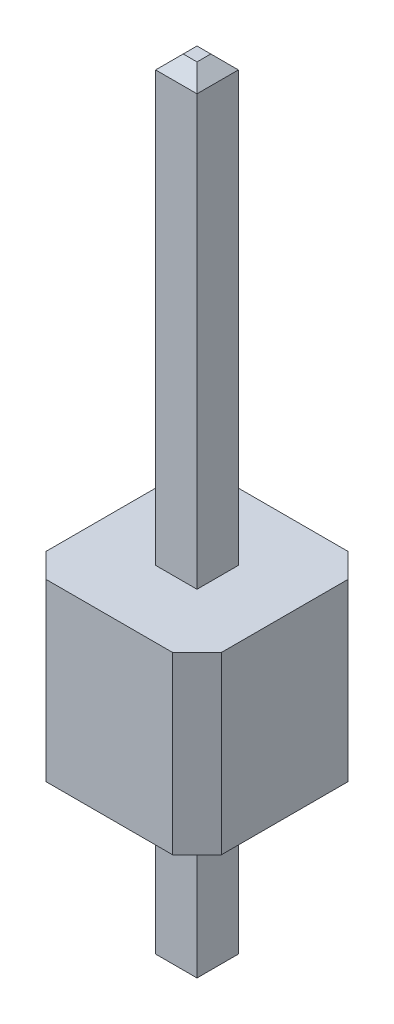
SolidWorks part; units mm, degrees
ref_plane "Alzado" through (0, 0, 0) normal (0, 0, 1) x (1, 0, 0)
ref_plane "Planta" through (0, 0, 0) normal (0, 1, 0) x (1, 0, 0)
ref_plane "Vista lateral" through (0, 0, 0) normal (1, 0, 0) x (0, 0, -1)
sketch "Sketch3" plane through (0, 0, 0) normal (0, 1, 0) x (1, 0, 0)
  line L1 (0.3, -0.3) -> (-0.3, -0.3)
  line L2 (0.3, -0.3) -> (0.3, 0.3)
  line L3 (0.3, 0.3) -> (-0.3, 0.3)
  line L4 (-0.3, -0.3) -> (-0.3, 0.3)
  line L5 (0.3, -0.3) -> (-0.3, 0.3) construction
  line L6 (0.3, 0.3) -> (-0.3, -0.3) construction
  point P0 (0, 0)
  dimension "D1" = 0.6
extrude "Boss-Extrude3" add sketch "Sketch3" along normal blind 11.5
chamfer "Chamfer2" distance 0.2 angle 45 8 edges at (0, 11.5, -0.3) (0.3, 11.5, 0) (0, 11.5, 0.3) (-0.3, 11.5, 0) (0, 0, 0.3) (0.3, 0, 0) (0, 0, -0.3) (-0.3, 0, 0)
ref_plane "Plane2" through (0, 2.54, 0) normal (0, 1, 0) x (1, 0, 0)
sketch "Sketch2" plane through (0, 2.54, 0) normal (0, 1, 0) x (1, 0, 0)
  line L0 (-0.9164, 1.27) -> (-1.27, 0.9164)
  line L1 (0.9164, -1.27) -> (-0.9164, -1.27)
  line L2 (1.27, -0.9164) -> (1.27, 0.9164)
  line L3 (0.9164, 1.27) -> (-0.9164, 1.27)
  line L4 (-1.27, -0.9164) -> (-1.27, 0.9164)
  line L5 (0, 1.27) -> (0, -1.27) construction
  line L7 (1.27, 0.9164) -> (0.9164, 1.27)
  line L8 (1.27, -0.9164) -> (0.9164, -1.27)
  line L9 (-0.9164, -1.27) -> (-1.27, -0.9164)
  line L10 (-1.27, 0) -> (1.27, 0) construction
  point P0 (0, 0)
  dimension "D1" = 2.54
  dimension "D2" = 0.5
extrude "Boss-Extrude4" add sketch "Sketch2" along normal blind 2.54
ref_axis "Axis1" through (0, 12.075, 0) along (0, -1, 0)
